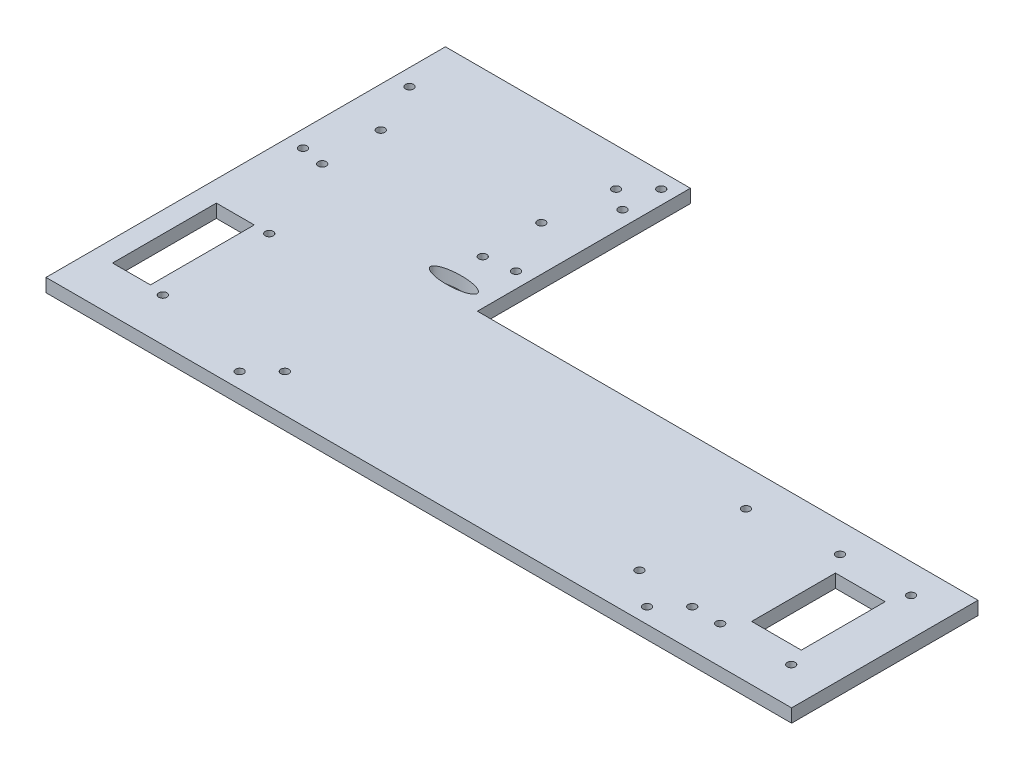
SolidWorks part; units mm, degrees
ref_plane "Front Plane" through (0, 0, 0) normal (0, 0, 1) x (1, 0, 0)
ref_plane "Top Plane" through (0, 0, 0) normal (0, 1, 0) x (1, 0, 0)
ref_plane "Right Plane" through (0, 0, 0) normal (1, 0, 0) x (0, 0, -1)
sketch "Sketch1" plane through (0, 0, 0) normal (0, 1, 0) x (1, 0, 0)
  line L1 (-124.5552, -60.7829) -> (155.4448, -60.7829)
  line L2 (-124.5552, -60.7829) -> (-124.5552, 9.2171)
  line L4 (155.4448, -60.7829) -> (155.4448, 9.2171)
  line L6 (-124.5552, 9.2171) -> (-124.5552, 89.2171)
  line L7 (-124.5552, 89.2171) -> (-32.5552, 89.2171)
  line L8 (-32.5552, 9.2171) -> (-32.5552, 89.2171)
  line L9 (119.8304, -40.1838) -> (138.4894, -40.1838)
  line L10 (119.8304, -40.1838) -> (119.8304, -8.6968)
  line L11 (119.8304, -8.6968) -> (138.4894, -8.6968)
  line L12 (138.4894, -40.1838) -> (138.4894, -8.6968)
  line L13 (-102.5012, -43.6237) -> (-116.7318, -43.6237)
  line L14 (-102.5012, -43.6237) -> (-102.5012, -4.6239)
  line L15 (-102.5012, -4.6239) -> (-116.7318, -4.6239)
  line L16 (-116.7318, -43.6237) -> (-116.7318, -4.6239)
  line L17 (-102.5012, -43.6237) -> (-116.7318, -4.6239) construction
  line L18 (-102.5012, -4.6239) -> (-116.7318, -43.6237) construction
  line L23 (-32.5552, 9.2171) -> (155.4448, 9.2171)
  circle A0 centre (141.3001, -46.7829) radius 1.5
  circle A1 centre (141.3001, -1.7829) radius 1.5
  circle A2 centre (114.6202, -1.7829) radius 1.5
  circle A3 centre (114.6202, -46.7829) radius 1.5
  circle A4 centre (82.1195, -44.6239) radius 1.5
  circle A5 centre (82.1195, -4.6239) radius 1.5
  circle A6 centre (-96.8805, -44.5794) radius 1.5
  circle A7 centre (-96.8805, -4.6239) radius 1.5
  circle A8 centre (-49.1247, -46.5403) radius 1.5
  circle A9 centre (-57.61, -55.0256) radius 1.5
  circle A10 centre (95.3972, -55.0306) radius 1.5
  circle A11 centre (103.8825, -46.5453) radius 1.5
  circle A12 centre (-37.7523, 83.4597) radius 1.5
  circle A13 centre (-46.2375, 74.9744) radius 1.5
  circle A14 centre (-118.3269, 69.4953) radius 1.5
  circle A15 centre (-118.3269, 29.4953) radius 1.5
  circle A16 centre (-38.3269, 29.4953) radius 1.5
  circle A17 centre (-38.3269, 69.4953) radius 1.5
  circle A18 centre (-109.6165, 49.9907) radius 1.5
  circle A19 centre (-109.6165, 27.9907) radius 1.5
  circle A20 centre (-49.3165, 49.9907) radius 1.5
  circle A21 centre (-49.3165, 27.9907) radius 1.5
  ellipse E0 centre (-47.12, 14.9456) end of major axis (-38.3269, 14.9456) minor radius 2.7964
  point P77 (-109.6165, -24.1238)
  dimension "D5" = 3
  dimension "D6" = 3
  dimension "D7" = 3
  dimension "D8" = 3
  dimension "D9" = 3
  dimension "D10" = 3
  dimension "D11" = 3
  dimension "D12" = 3
  dimension "D13" = 3
  dimension "D14" = 3
  dimension "D1" = 280
  dimension "D2" = 70
  dimension "D3" = 92
  dimension "D4" = 150
extrude "Boss-Extrude1" add sketch "Sketch1" along normal blind 5 contours L1 L4 L2 | L8 L7 L6 region at (-11.1732, 0, 4.5855)
